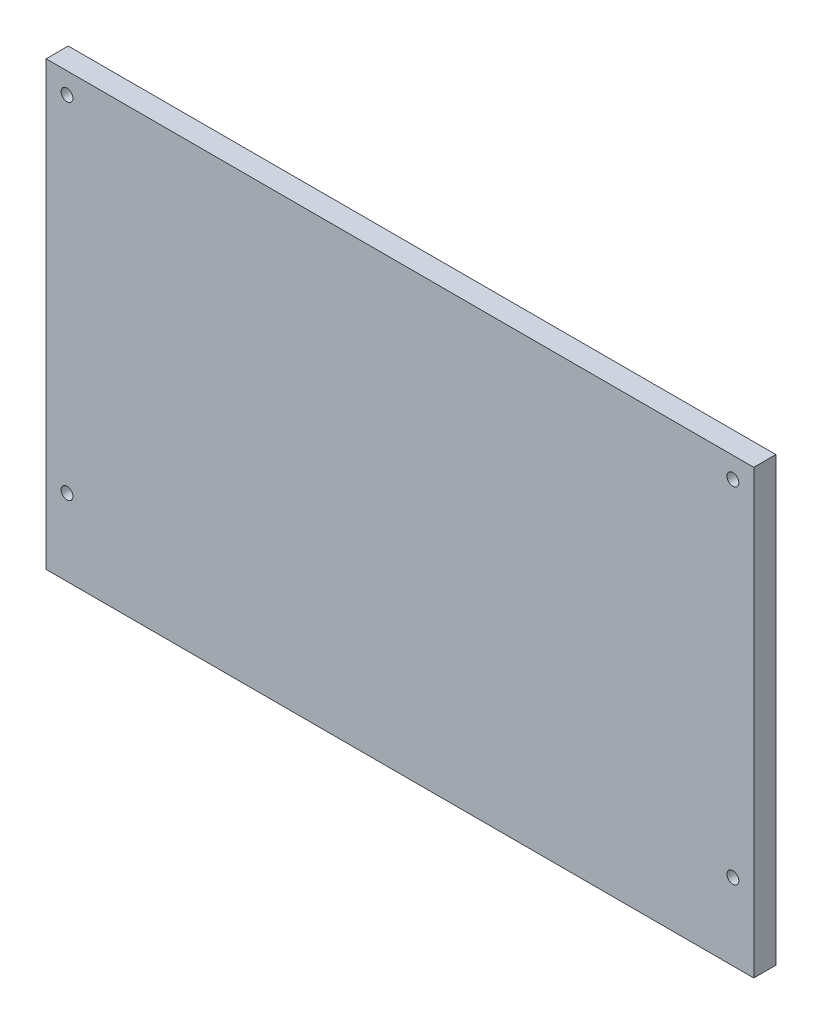
SolidWorks part; units mm, degrees
material "Acrylic (Medium-high impact)"
ref_plane "Front Plane" through (0, 0, 0) normal (0, 0, 1) x (1, 0, 0)
ref_plane "Top Plane" through (0, 0, 0) normal (0, 1, 0) x (1, 0, 0)
ref_plane "Right Plane" through (0, 0, 0) normal (1, 0, 0) x (0, 0, -1)
sketch "Sketch1" plane through (0, 0, 0) normal (0, 0, 1) x (1, 0, 0)
  line L1 (203.2, 127) -> (0, 127)
  line L2 (203.2, 127) -> (203.2, 0)
  line L3 (203.2, 0) -> (0, 0)
  line L4 (0, 127) -> (0, 0)
  line L5 (203.2, 127) -> (0, 0) construction
  line L6 (203.2, 0) -> (0, 127) construction
  point P0 (101.6, 63.5)
  dimension "D1" = 127
  dimension "D2" = 203.2
extrude "Boss-Extrude1" add sketch "Sketch1" along normal blind 6.35
hole_wizard "M3 Clearance Hole1" positions "Sketch2" profile "Sketch3" hole size "M3" standard "ANSI Metric" end condition through all
sketch "Sketch2" plane through (0, 0, 6.35) normal (0, 0, 1) x (1, 0, 0)
  line L0 (0, 127) -> (0, 0) construction
  line L1 (203.2, 127) -> (0, 127) construction
  line L2 (203.2, 0) -> (203.2, 127) construction
  line L3 (0, 0) -> (203.2, 0) construction
  point P0 (5.9944, 121.0056)
  point P2 (5.9944, 21.9964)
  point P4 (197.2056, 21.9964)
  point P6 (197.2056, 121.0056)
  dimension "D1" = 5.9944
  dimension "D2" = 5.9944
  dimension "D3" = 5.9944
  dimension "D4" = 21.9964
sketch "Sketch3" plane through (5.9944, 121.0056, 6.35) normal (1, 0, 0) x (0, -1, 0)
  line L0 (0, 0) -> (0, 6.35)
  line L1 (0, 6.35) -> (1.7, 6.35)
  line L2 (1.7, 6.35) -> (1.7, 0)
  line L5 (1.7, 0) -> (0, 0)
  line L11 (0, -6.35) -> (0, 107.95) construction
  dimension "Thru Hole Dia." = 3.4
  dimension "Thru Hole Depth" = 6.35
sketch "Sketch4" plane through (0, 0, 6.35) normal (0, 0, 1) x (1, 0, 0)
  line L0 (0, 127) -> (0, 0) construction
  line L1 (46.99, 107.95) -> (50.4952, 107.95)
  line L2 (46.99, 107.95) -> (46.99, 44.45)
  line L3 (46.99, 44.45) -> (50.4952, 44.45)
  line L4 (50.4952, 107.95) -> (50.4952, 44.45)
  line L5 (152.7048, 107.95) -> (156.21, 107.95)
  line L6 (152.7048, 107.95) -> (152.7048, 44.45)
  line L7 (152.7048, 44.45) -> (156.21, 44.45)
  line L8 (156.21, 107.95) -> (156.21, 44.45)
  line L9 (203.2, 0) -> (203.2, 127) construction
  line L10 (203.2, 127) -> (0, 127) construction
  dimension "D1" = 3.5052
  dimension "D2" = 63.5
  dimension "D3" = 46.99
  dimension "D4" = 46.99
  dimension "D5" = 19.05
extrude "Cut-Extrude1" [suppressed] cut sketch "Sketch4" against normal through all
sketch "Sketch5" plane through (0, 0, 6.35) normal (0, 0, 1) x (1, 0, 0)
  line L0 (0, 10.7092) -> (76.2, 0)
  line L1 (0, 127) -> (0, 0) construction
  line L2 (0, 0) -> (203.2, 0) construction
  line L3 (76.2, 0) -> (0, 0)
  line L4 (0, 0) -> (0, 10.7092)
  line L5 (127, 0) -> (203.2, 0)
  line L6 (203.2, 0) -> (203.2, 10.7092)
  line L7 (203.2, 0) -> (203.2, 127) construction
  line L8 (203.2, 10.7092) -> (127, 0)
  dimension "D1" = 8
  dimension "D2" = 8
  dimension "D3" = 76.2
  dimension "D4" = 76.2
extrude "Cut-Extrude2" [suppressed] cut sketch "Sketch5" against normal through all
